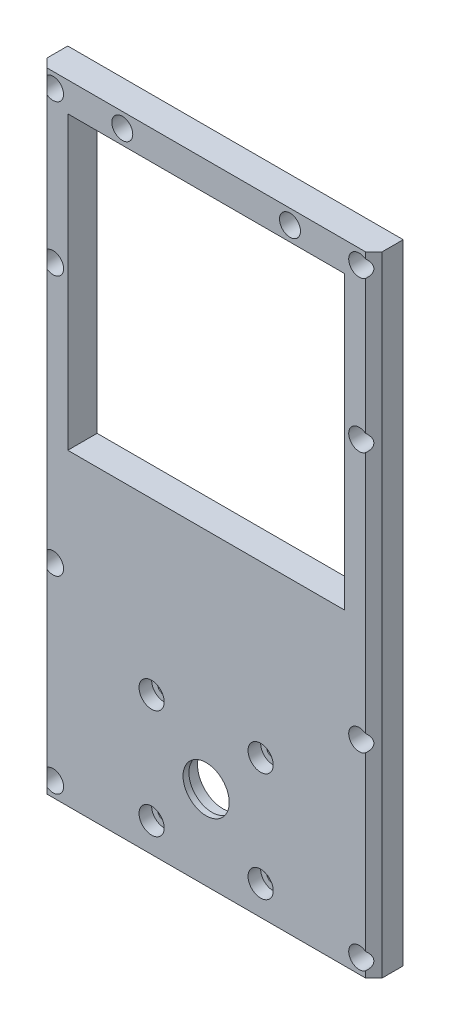
SolidWorks part; units mm, degrees
ref_plane "Front Plane" through (0, 0, 0) normal (0, 0, 1) x (1, 0, 0)
ref_plane "Top Plane" through (0, 0, 0) normal (0, 1, 0) x (1, 0, 0)
ref_plane "Right Plane" through (0, 0, 0) normal (1, 0, 0) x (0, 0, -1)
sketch "Sketch1" plane through (0, 0, 0) normal (0, 0, 1) x (1, 0, 0)
  line L1 (-40, -75) -> (40, -75)
  line L2 (-40, -75) -> (-40, 75)
  line L3 (-40, 75) -> (40, 75)
  line L4 (40, -75) -> (40, 75)
  line L5 (-40, -75) -> (40, 75) construction
  line L6 (-40, 75) -> (40, -75) construction
  line L7 (-33, -68) -> (33, -68)
  line L8 (-33, -68) -> (-33, 68)
  line L9 (-33, 68) -> (33, 68)
  line L10 (33, -68) -> (33, 68)
  line L11 (-33, -68) -> (33, 68) construction
  line L12 (-33, 68) -> (33, -68) construction
  point P0 (0, 0)
  point P6 (0, 0)
  dimension "D1" = 150
  dimension "D2" = 80
  dimension "D3" = 7
  dimension "D4" = 7
extrude "Boss-Extrude1" add sketch "Sketch1" along normal blind 7
sketch "Sketch2" plane through (0, 0, 7) normal (0, 0, 1) x (1, 0, 0)
  line L0 (33, -68) -> (33, 68) construction
  line L1 (-33, -68) -> (33, -68)
  line L2 (-33, -68) -> (-33, -32)
  line L3 (-33, -32) -> (33, -32)
  line L4 (33, -68) -> (33, -32)
  dimension "D1" = 36
extrude "Boss-Extrude2" add sketch "Sketch2" against normal up to surface (7 mm away) up to face at (0, 0, 0)
sketch "Sketch3" plane through (0, 0, 0) normal (0, 0, -1) x (-1, 0, 0)
  line L0 (0, -75) -> (0, -55) construction
  line L1 (40, -75) -> (-40, -75) construction
  circle A0 centre (0, -55) radius 5.5
  dimension "D1" = 11
  dimension "D2" = 20
extrude "Cut-Extrude1" cut sketch "Sketch3" against normal through all
sketch "Sketch4" plane through (0, 0, 0) normal (0, 0, -1) x (-1, 0, 0)
  circle A0 centre (0, -55) radius 6.05
  dimension "D1" = 12.1
extrude "Cut-Extrude2" cut sketch "Sketch4" against normal offset from surface (5.6 mm away) 1.4 up to face at (-5.5, -55, 7)
sketch "Sketch5" plane through (0, 0, 0) normal (0, 0, -1) x (-1, 0, 0)
  circle A0 centre (0, -55) radius 11
  dimension "D1" = 22
extrude "Cut-Extrude3" cut sketch "Sketch5" against normal offset from surface (3 mm away) 2.6 up to face at (-6.05, -55, 5.6)
sketch "Sketch6" plane through (0, 0, 0) normal (0, 0, -1) x (-1, 0, 0)
  line L1 (-13, -68) -> (13, -68) construction
  line L2 (-13, -68) -> (-13, -42) construction
  line L3 (-13, -42) -> (13, -42) construction
  line L4 (13, -68) -> (13, -42) construction
  line L5 (-13, -68) -> (13, -42) construction
  line L6 (-13, -42) -> (13, -68) construction
  circle A0 centre (-13, -42) radius 1.6
  circle A1 centre (13, -42) radius 1.6
  circle A2 centre (13, -68) radius 1.6
  circle A3 centre (-13, -68) radius 1.6
  point P0 (0, -55)
  dimension "D2" = 3.2
  dimension "D1" = 26
extrude "Cut-Extrude4" cut sketch "Sketch6" against normal through all
sketch "Sketch7" plane through (0, 0, 0) normal (0, 0, -1) x (-1, 0, 0)
  line L1 (-25, -74) -> (25, -74)
  line L2 (-25, -74) -> (-25, -36)
  line L3 (-25, -36) -> (25, -36)
  line L4 (25, -74) -> (25, -36)
  line L5 (-25, -74) -> (25, -36) construction
  line L6 (-25, -36) -> (25, -74) construction
  point P0 (0, -55)
  dimension "D1" = 50
  dimension "D2" = 38
extrude "Cut-Extrude5" cut sketch "Sketch7" against normal blind 1
sketch "Sketch8" plane through (0, 0, 7) normal (0, 0, 1) x (1, 0, 0)
  circle A0 centre (-13, -42) radius 3
  circle A1 centre (13, -42) radius 3
  circle A2 centre (13, -68) radius 3
  circle A3 centre (-13, -68) radius 3
  dimension "D1" = 6
extrude "Cut-Extrude6" cut sketch "Sketch8" against normal blind 3
sketch "Sketch9" plane through (0, 0, 7) normal (0, 0, 1) x (1, 0, 0)
  line L0 (-40, 75) -> (-40, -75) construction
  line L1 (-36.5, -71.5) -> (36.5, -71.5) construction
  line L2 (-36.5, -71.5) -> (-36.5, 71.5) construction
  line L3 (-36.5, 71.5) -> (36.5, 71.5) construction
  line L4 (36.5, -71.5) -> (36.5, 71.5) construction
  line L5 (-36.5, -71.5) -> (36.5, 71.5) construction
  line L6 (-36.5, 71.5) -> (36.5, -71.5) construction
  line L7 (40, 75) -> (-40, 75) construction
  circle A0 centre (-36.5, 71.5) radius 1.35
  circle A1 centre (36.5, 71.5) radius 1.35
  circle A4 centre (-36.5, -71.5) radius 1.35
  circle A5 centre (36.5, -71.5) radius 1.35
  circle A6 centre (-36.5, 35.5) radius 1.35
  circle A7 centre (36.5, 35.5) radius 1.35
  circle A8 centre (36.5, -26.5) radius 1.35
  circle A9 centre (-36.5, -26.5) radius 1.35
  point P0 (0, 0)
  dimension "D3" = 2.7
  dimension "D1" = 3.5
  dimension "D2" = 3.5
  dimension "D4" = 45
  dimension "D5" = 36
extrude "Cut-Extrude7" cut sketch "Sketch9" against normal through all
sketch "Sketch10" plane through (0, 0, 7) normal (0, 0, 1) x (1, 0, 0)
  circle A0 centre (-36.5, 71.5) radius 2.5
  circle A1 centre (36.5, 35.5) radius 2.5
  circle A2 centre (-36.5, 35.5) radius 2.5
  circle A3 centre (36.5, 71.5) radius 2.5
  circle A4 centre (-36.5, -71.5) radius 2.5
  circle A5 centre (36.5, -71.5) radius 2.5
  circle A6 centre (-36.5, -26.5) radius 2.5
  circle A7 centre (36.5, -26.5) radius 2.5
  dimension "D1" = 5
extrude "Cut-Extrude8" cut sketch "Sketch10" against normal blind 5
chamfer "Chamfer1" distance 2 angle 45 2 edges at (-40, 0, 7) (40, 0, 7)
sketch "Sketch11" plane through (0, 0, 7) normal (0, 0, 1) x (1, 0, 0)
  line L0 (33, -32) -> (33, 68) construction
  line L1 (-33, -32) -> (33, -32)
  line L2 (-33, -32) -> (-33, -1.5)
  line L3 (-33, -1.5) -> (33, -1.5)
  line L4 (33, -32) -> (33, -1.5)
  line L5 (-38, -75) -> (38, -75) construction
  dimension "D1" = 73.5
extrude "Boss-Extrude3" add sketch "Sketch11" against normal up to surface (7 mm away) up to face at (-35.15, -71.5, 0)
sketch "Sketch12" plane through (0, 0, 7) normal (0, 0, 1) x (1, 0, 0)
  line L0 (-36.5, 71.5) -> (36.5, 71.5) construction
  line L1 (-20, 71.5) -> (20, 71.5) construction
  circle A0 centre (-20, 71.5) radius 1.35
  circle A1 centre (20, 71.5) radius 1.35
  circle A2 centre (-36.5, 71.5) radius 1.35 construction
  point P7 (0, 71.5)
  dimension "D1" = 40
extrude "Cut-Extrude9" cut sketch "Sketch12" against normal through all
sketch "Sketch13" plane through (0, 0, 7) normal (0, 0, 1) x (1, 0, 0)
  circle A0 centre (-20, 71.5) radius 2.5
  circle A1 centre (20, 71.5) radius 2.5
  arc A2 (-38, 69.5) -> (-38, 73.5) centre (-36.5, 71.5) ccw construction
extrude "Cut-Extrude10" cut sketch "Sketch13" against normal up to surface (5 mm away) up to face at (-34, 71.5, 2)
